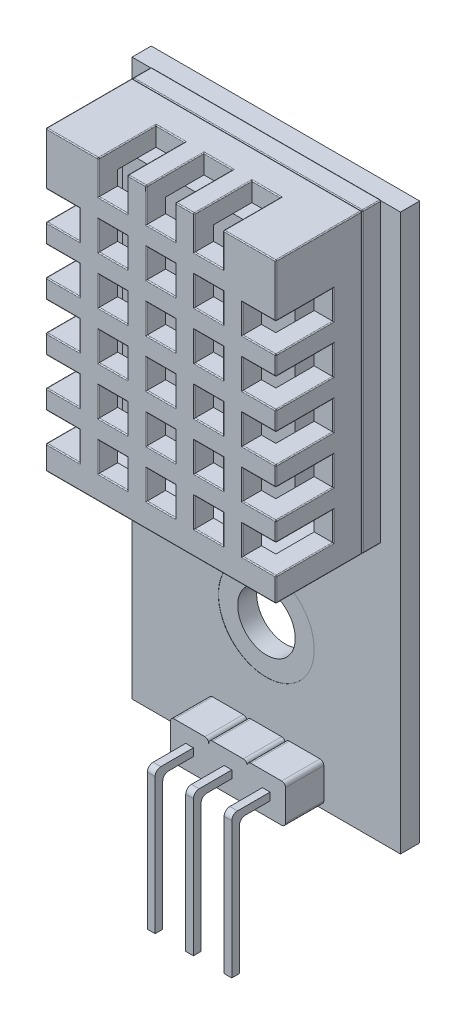
SolidWorks part; units mm, degrees
ref_plane "Front Plane" through (0, 0, 0) normal (0, 0, 1) x (1, 0, 0)
ref_plane "Top Plane" through (0, 0, 0) normal (0, 1, 0) x (1, 0, 0)
ref_plane "Right Plane" through (0, 0, 0) normal (1, 0, 0) x (0, 0, -1)
sketch "Sketch1" plane through (0, 0, 0) normal (0, 0, 1) x (1, 0, 0)
  line L1 (0, 0) -> (12, 0)
  line L2 (0, 0) -> (0, 15.5)
  line L3 (0, 15.5) -> (12, 15.5)
  line L4 (12, 0) -> (12, 15.5)
  dimension "D1" = 12
  dimension "D2" = 15.5
extrude "Boss-Extrude1" add sketch "Sketch1" along normal blind 5.5
shell "Shell2" thickness 1 removed face at (6, 7.75, 0)
sketch "Sketch3" plane through (0, 0, 5.5) normal (0, 0, 1) x (1, 0, 0)
  line L0 (12, 15.5) -> (0, 15.5) construction
  line L1 (2.75, 15.5) -> (4.25, 15.5)
  line L2 (2.75, 15.5) -> (2.75, 13.75)
  line L3 (2.75, 13.75) -> (4.25, 13.75)
  line L4 (4.25, 15.5) -> (4.25, 13.75)
  line L5 (5.25, 15.5) -> (6.75, 15.5)
  line L6 (5.25, 15.5) -> (5.25, 13.75)
  line L7 (5.25, 13.75) -> (6.75, 13.75)
  line L8 (6.75, 15.5) -> (6.75, 13.75)
  line L9 (7.75, 15.5) -> (9.25, 15.5)
  line L10 (7.75, 15.5) -> (7.75, 13.75)
  line L11 (7.75, 13.75) -> (9.25, 13.75)
  line L12 (9.25, 15.5) -> (9.25, 13.75)
  line L13 (0, 15.5) -> (0, 0) construction
  dimension "D1" = 1.5
  dimension "D2" = 1.75
  dimension "D4" = 2.75
  dimension "D3" = 3
extrude "Cut-Extrude1" cut sketch "Sketch3" against normal blind 3
sketch "Sketch4" plane through (0, 0, 5.5) normal (0, 0, 1) x (1, 0, 0)
  line L0 (2.75, 13.75) -> (4.25, 13.75) construction
  line L1 (2.75, 12.75) -> (4.25, 12.75)
  line L2 (2.75, 12.75) -> (2.75, 11.25)
  line L3 (2.75, 11.25) -> (4.25, 11.25)
  line L4 (4.25, 12.75) -> (4.25, 11.25)
  line L5 (0, 15.5) -> (0, 0) construction
  line L6 (5.25, 12.75) -> (6.75, 12.75)
  line L7 (5.25, 12.75) -> (5.25, 11.25)
  line L8 (5.25, 11.25) -> (6.75, 11.25)
  line L9 (6.75, 12.75) -> (6.75, 11.25)
  line L10 (7.75, 12.75) -> (9.25, 12.75)
  line L11 (7.75, 12.75) -> (7.75, 11.25)
  line L12 (7.75, 11.25) -> (9.25, 11.25)
  line L13 (9.25, 12.75) -> (9.25, 11.25)
  line L14 (5.25, 10.25) -> (6.75, 10.25)
  line L15 (5.25, 10.25) -> (5.25, 8.75)
  line L16 (5.25, 8.75) -> (6.75, 8.75)
  line L17 (6.75, 10.25) -> (6.75, 8.75)
  line L18 (7.75, 10.25) -> (9.25, 10.25)
  line L19 (7.75, 10.25) -> (7.75, 8.75)
  line L20 (7.75, 8.75) -> (9.25, 8.75)
  line L21 (9.25, 10.25) -> (9.25, 8.75)
  line L22 (5.25, 7.75) -> (6.75, 7.75)
  line L23 (5.25, 7.75) -> (5.25, 6.25)
  line L24 (5.25, 6.25) -> (6.75, 6.25)
  line L25 (6.75, 7.75) -> (6.75, 6.25)
  line L26 (7.75, 7.75) -> (9.25, 7.75)
  line L27 (7.75, 7.75) -> (7.75, 6.25)
  line L28 (7.75, 6.25) -> (9.25, 6.25)
  line L29 (9.25, 7.75) -> (9.25, 6.25)
  line L30 (5.25, 5.25) -> (6.75, 5.25)
  line L31 (5.25, 5.25) -> (5.25, 3.75)
  line L32 (5.25, 3.75) -> (6.75, 3.75)
  line L33 (6.75, 5.25) -> (6.75, 3.75)
  line L34 (7.75, 5.25) -> (9.25, 5.25)
  line L35 (7.75, 5.25) -> (7.75, 3.75)
  line L36 (7.75, 3.75) -> (9.25, 3.75)
  line L37 (9.25, 5.25) -> (9.25, 3.75)
  line L38 (5.25, 2.75) -> (6.75, 2.75)
  line L39 (5.25, 2.75) -> (5.25, 1.25)
  line L40 (5.25, 1.25) -> (6.75, 1.25)
  line L41 (6.75, 2.75) -> (6.75, 1.25)
  line L42 (7.75, 2.75) -> (9.25, 2.75)
  line L43 (7.75, 2.75) -> (7.75, 1.25)
  line L44 (7.75, 1.25) -> (9.25, 1.25)
  line L45 (9.25, 2.75) -> (9.25, 1.25)
  line L46 (2.75, 10.25) -> (4.25, 10.25)
  line L47 (2.75, 10.25) -> (2.75, 8.75)
  line L48 (2.75, 8.75) -> (4.25, 8.75)
  line L49 (4.25, 10.25) -> (4.25, 8.75)
  line L50 (2.75, 7.75) -> (4.25, 7.75)
  line L51 (2.75, 7.75) -> (2.75, 6.25)
  line L52 (2.75, 6.25) -> (4.25, 6.25)
  line L53 (4.25, 7.75) -> (4.25, 6.25)
  line L54 (2.75, 5.25) -> (4.25, 5.25)
  line L55 (2.75, 5.25) -> (2.75, 3.75)
  line L56 (2.75, 3.75) -> (4.25, 3.75)
  line L57 (4.25, 5.25) -> (4.25, 3.75)
  line L58 (2.75, 2.75) -> (4.25, 2.75)
  line L59 (2.75, 2.75) -> (2.75, 1.25)
  line L60 (2.75, 1.25) -> (4.25, 1.25)
  line L61 (4.25, 2.75) -> (4.25, 1.25)
  dimension "D1" = 1.5
  dimension "D2" = 1
  dimension "D3" = 2.75
  dimension "D4" = 3
  dimension "D5" = 5
extrude "Cut-Extrude2" cut sketch "Sketch4" against normal blind 3
sketch "Sketch5" plane through (0, 0, 5.5) normal (0, 0, 1) x (1, 0, 0)
  line L0 (0, 15.5) -> (0, 0) construction
  line L1 (0, 12.75) -> (1.75, 12.75)
  line L2 (0, 12.75) -> (0, 11.25)
  line L3 (0, 11.25) -> (1.75, 11.25)
  line L4 (1.75, 12.75) -> (1.75, 11.25)
  line L7 (2.75, 12.75) -> (2.75, 11.25) construction
  line L8 (10.25, 12.75) -> (12, 12.75)
  line L9 (10.25, 12.75) -> (10.25, 11.25)
  line L10 (10.25, 11.25) -> (12, 11.25)
  line L11 (12, 12.75) -> (12, 11.25)
  line L12 (10.25, 10.25) -> (12, 10.25)
  line L13 (10.25, 10.25) -> (10.25, 8.75)
  line L14 (10.25, 8.75) -> (12, 8.75)
  line L15 (12, 10.25) -> (12, 8.75)
  line L16 (10.25, 7.75) -> (12, 7.75)
  line L17 (10.25, 7.75) -> (10.25, 6.25)
  line L18 (10.25, 6.25) -> (12, 6.25)
  line L19 (12, 7.75) -> (12, 6.25)
  line L20 (10.25, 5.25) -> (12, 5.25)
  line L21 (10.25, 5.25) -> (10.25, 3.75)
  line L22 (10.25, 3.75) -> (12, 3.75)
  line L23 (12, 5.25) -> (12, 3.75)
  line L24 (10.25, 2.75) -> (12, 2.75)
  line L25 (10.25, 2.75) -> (10.25, 1.25)
  line L26 (10.25, 1.25) -> (12, 1.25)
  line L27 (12, 2.75) -> (12, 1.25)
  line L28 (0, 10.25) -> (1.75, 10.25)
  line L29 (0, 10.25) -> (0, 8.75)
  line L30 (0, 8.75) -> (1.75, 8.75)
  line L31 (1.75, 10.25) -> (1.75, 8.75)
  line L32 (0, 7.75) -> (1.75, 7.75)
  line L33 (0, 7.75) -> (0, 6.25)
  line L34 (0, 6.25) -> (1.75, 6.25)
  line L35 (1.75, 7.75) -> (1.75, 6.25)
  line L36 (0, 5.25) -> (1.75, 5.25)
  line L37 (0, 5.25) -> (0, 3.75)
  line L38 (0, 3.75) -> (1.75, 3.75)
  line L39 (1.75, 5.25) -> (1.75, 3.75)
  line L40 (0, 2.75) -> (1.75, 2.75)
  line L41 (0, 2.75) -> (0, 1.25)
  line L42 (0, 1.25) -> (1.75, 1.25)
  line L43 (1.75, 2.75) -> (1.75, 1.25)
  dimension "D1" = 1
  dimension "D2" = 2
  dimension "D3" = 5
extrude "Cut-Extrude3" cut sketch "Sketch5" against normal blind 3
sketch "Sketch6" plane through (0, 0, 0) normal (0, 0, -1) x (-1, 0, 0)
  line L4 (0, 0) -> (0, 15.5)
  line L5 (0, 15.5) -> (-12, 15.5)
  line L6 (-12, 15.5) -> (-12, 0)
  line L7 (-12, 0) -> (0, 0)
  line L8 (0, 0) -> (0, 15.5)
  line L9 (0, 15.5) -> (-12, 15.5)
  line L10 (-12, 15.5) -> (-12, 0)
  line L11 (-12, 0) -> (0, 0)
  line L12 (-1, 14.5) -> (-11, 14.5)
  line L13 (-1, 1) -> (-1, 14.5)
  line L14 (-11, 1) -> (-1, 1)
  line L15 (-11, 14.5) -> (-11, 1)
  line L16 (-1, 14.5) -> (-11, 14.5)
  line L17 (-1, 1) -> (-1, 14.5)
  line L18 (-11, 1) -> (-1, 1)
  line L19 (-11, 14.5) -> (-11, 1)
  dimension "D1" = 0
  dimension "D2" = 0
extrude "Cut-Extrude4" cut sketch "Sketch6" against normal blind 1
ref_plane "Plane1" through (0, 0, 0.99) normal (0, 0, 1) x (1, 0, 0)
sketch "Sketch8" plane through (0, 0, 0.99) normal (0, 0, 1) x (1, 0, 0)
  line L4 (0, 0) -> (12, 0)
  line L5 (0, 15.5) -> (0, 0)
  line L6 (12, 15.5) -> (0, 15.5)
  line L7 (12, 0) -> (12, 15.5)
  line L8 (0, 0) -> (12, 0)
  line L9 (0, 15.5) -> (0, 0)
  line L10 (12, 15.5) -> (0, 15.5)
  line L11 (12, 0) -> (12, 15.5)
  dimension "D1" = 0
extrude "Boss-Extrude3" add sketch "Sketch8" against normal blind 0.99 separate body
fillet "Fillet1" radius 0.05 163 edges at (6, 0, 1) (0, 12.75, 4) (0, 12, 2.5) (0, 11.25, 4) (0, 10.25, 4) (0, 9.5, 2.5) (0, 8.75, 4) (0, 7.75, 4) (0, 7, 2.5) (0, 6.25, 4) (0, 5.25, 4) (0, 4.5, 2.5) (0, 3.75, 4) (0, 2.75, 4) (0, 2, 2.5) (0, 1.25, 4) (0, 0, 3.25) (0, 7.75, 1) (9.25, 15.5, 4) (8.5, 15.5, 2.5) (7.75, 15.5, 4) (6.75, 15.5, 4) (6, 15.5, 2.5) (5.25, 15.5, 4) (4.25, 15.5, 4) (3.5, 15.5, 2.5) (2.75, 15.5, 4) (0, 15.5, 3.25) (6, 15.5, 1) (12, 0, 3.25) (12, 1.25, 4) (12, 2, 2.5) (12, 2.75, 4) (12, 3.75, 4) (12, 4.5, 2.5) (12, 5.25, 4) (12, 6.25, 4) (12, 7, 2.5) (12, 7.75, 4) (12, 8.75, 4) (12, 9.5, 2.5) (12, 10.25, 4) (12, 11.25, 4) (12, 12, 2.5) (12, 12.75, 4) (12, 15.5, 3.25) (12, 7.75, 1) (0.875, 3.75, 5.5) (1.75, 4.5, 5.5) (0.875, 5.25, 5.5) (0, 5.75, 5.5) (0.875, 6.25, 5.5) (1.75, 7, 5.5) (0.875, 7.75, 5.5) (0, 8.25, 5.5) (0.875, 8.75, 5.5) (1.75, 9.5, 5.5) (0.875, 10.25, 5.5) (0, 10.75, 5.5) (0.875, 11.25, 5.5) (1.75, 12, 5.5) (0.875, 12.75, 5.5) (0, 14.125, 5.5) (1.375, 15.5, 5.5) (2.75, 14.625, 5.5) (3.5, 13.75, 5.5) (4.25, 14.625, 5.5) (4.75, 15.5, 5.5) (5.25, 14.625, 5.5) (6, 13.75, 5.5) (6.75, 14.625, 5.5) (7.25, 15.5, 5.5) (7.75, 14.625, 5.5) (8.5, 13.75, 5.5) (9.25, 14.625, 5.5) (10.625, 15.5, 5.5) (12, 14.125, 5.5) (11.125, 12.75, 5.5) (10.25, 12, 5.5) (11.125, 11.25, 5.5) (12, 10.75, 5.5) (11.125, 10.25, 5.5) (10.25, 9.5, 5.5) (11.125, 8.75, 5.5) (12, 8.25, 5.5) (11.125, 7.75, 5.5) (10.25, 7, 5.5) (11.125, 6.25, 5.5) (12, 5.75, 5.5) (11.125, 5.25, 5.5) (10.25, 4.5, 5.5) (11.125, 3.75, 5.5) (12, 3.25, 5.5) (11.125, 2.75, 5.5) (10.25, 2, 5.5) (11.125, 1.25, 5.5) (12, 0.625, 5.5) (6, 0, 5.5) (0, 0.625, 5.5) (0.875, 1.25, 5.5) (1.75, 2, 5.5) (0.875, 2.75, 5.5) (0, 3.25, 5.5) (4.25, 12, 5.5) (3.5, 12.75, 5.5) (2.75, 12, 5.5) (3.5, 11.25, 5.5) (6.75, 12, 5.5) (6, 12.75, 5.5) (5.25, 12, 5.5) (6, 11.25, 5.5) (9.25, 12, 5.5) (8.5, 12.75, 5.5) (7.75, 12, 5.5) (8.5, 11.25, 5.5) (6.75, 9.5, 5.5) (6, 10.25, 5.5) (5.25, 9.5, 5.5) (6, 8.75, 5.5) (9.25, 9.5, 5.5) (8.5, 10.25, 5.5) (7.75, 9.5, 5.5) (8.5, 8.75, 5.5) (6.75, 7, 5.5) (6, 7.75, 5.5) (5.25, 7, 5.5) (6, 6.25, 5.5) (9.25, 7, 5.5) (8.5, 7.75, 5.5) (7.75, 7, 5.5) (8.5, 6.25, 5.5) (6.75, 4.5, 5.5) (6, 5.25, 5.5) (5.25, 4.5, 5.5) (6, 3.75, 5.5) (9.25, 4.5, 5.5) (8.5, 5.25, 5.5) (7.75, 4.5, 5.5) (8.5, 3.75, 5.5) (6.75, 2, 5.5) (6, 2.75, 5.5) (5.25, 2, 5.5) (6, 1.25, 5.5) (9.25, 2, 5.5) (8.5, 2.75, 5.5) (7.75, 2, 5.5) (8.5, 1.25, 5.5) (4.25, 9.5, 5.5) (3.5, 10.25, 5.5) (2.75, 9.5, 5.5) (3.5, 8.75, 5.5) (4.25, 7, 5.5) (3.5, 7.75, 5.5) (2.75, 7, 5.5) (3.5, 6.25, 5.5) (4.25, 4.5, 5.5) (3.5, 5.25, 5.5) (2.75, 4.5, 5.5) (3.5, 3.75, 5.5) (4.25, 2, 5.5) (3.5, 2.75, 5.5) (2.75, 2, 5.5) (3.5, 1.25, 5.5)
fillet "Fillet2" radius 0.05 12 edges at (6, 15.5, 0.99) (0, 15.5, 0.495) (0, 7.75, 0.99) (0, 0, 0.495) (6, 0, 0.99) (12, 15.5, 0.495) (12, 0, 0.495) (12, 7.75, 0.99) (6, 15.5, 0) (0, 7.75, 0) (6, 0, 0) (12, 7.75, 0)
sketch "Sketch10" plane through (0, 0, 0.99) normal (0, 0, 1) x (1, 0, 0)
  line L14 (1.5, 1.5) -> (10.5, 1.5)
  line L15 (10.5, 1.5) -> (10.5, 14)
  line L16 (10.5, 14) -> (1.5, 14)
  line L17 (1.5, 14) -> (1.5, 1.5)
  line L18 (1.5, 1.5) -> (10.5, 1.5)
  line L19 (10.5, 1.5) -> (10.5, 14)
  line L20 (10.5, 14) -> (1.5, 14)
  line L21 (1.5, 14) -> (1.5, 1.5)
  dimension "D1" = 0.5
extrude "Boss-Extrude4" add sketch "Sketch10" along normal blind 2
sketch "Sketch11" plane through (0, 0, 0) normal (0, 0, -1) x (-1, 0, 0)
  line L0 (-11.95, 0.05) -> (-0.05, 0.05) construction
  line L1 (-13, 15.45) -> (1, 15.45)
  line L2 (-13, 15.45) -> (-13, -13.55)
  line L3 (-13, -13.55) -> (1, -13.55)
  line L4 (1, 15.45) -> (1, -13.55)
  point P4 (-6, 15.45)
  point P7 (-6, 0.05)
  dimension "D1" = 14
  dimension "D2" = 29
  dimension "D3" = 0
  dimension "D4" = 14
extrude "Boss-Extrude5" add sketch "Sketch11" along normal blind 1
sketch "Sketch12" plane through (0, 0, 0) normal (0, 0, 1) x (1, 0, 0)
  line L2 (3, -11.55) -> (3, -13.15)
  line L4 (9, -11.55) -> (9, -13.15)
  line L5 (13, 15.45) -> (13, -13.55) construction
  line L7 (5, -11.55) -> (5, -13.15)
  line L8 (7, -11.55) -> (7, -13.15)
  line L9 (3.2, -11.35) -> (4.8, -11.35)
  line L10 (6.8, -11.35) -> (5.2, -11.35)
  line L11 (8.8, -11.35) -> (7.2, -11.35)
  line L12 (9, -13.35) -> (9, -11.35)
  line L13 (8.8, -13.35) -> (7.2, -13.35)
  line L14 (6.8, -13.35) -> (5.2, -13.35)
  line L15 (4.8, -13.35) -> (3.2, -13.35)
  arc A0 (3, -11.55) -> (3.2, -11.35) centre (3.2, -11.55) cw
  arc A1 (5, -11.55) -> (4.8, -11.35) centre (4.8, -11.55) ccw
  arc A2 (5, -11.55) -> (5.2, -11.35) centre (5.2, -11.55) cw
  arc A3 (3.2, -13.35) -> (3, -13.15) centre (3.2, -13.15) cw
  arc A4 (4.8, -13.35) -> (5, -13.15) centre (4.8, -13.15) ccw
  arc A5 (5, -13.15) -> (5.2, -13.35) centre (5.2, -13.15) ccw
  arc A6 (7, -13.15) -> (6.8, -13.35) centre (6.8, -13.15) cw
  arc A7 (7, -13.15) -> (7.2, -13.35) centre (7.2, -13.15) ccw
  arc A8 (7, -11.55) -> (6.8, -11.35) centre (6.8, -11.55) ccw
  arc A9 (7, -11.55) -> (7.2, -11.35) centre (7.2, -11.55) cw
  arc A10 (9, -11.55) -> (8.8, -11.35) centre (8.8, -11.55) ccw
  arc A11 (9, -13.15) -> (8.8, -13.35) centre (8.8, -13.15) cw
  point P8 (3, -11.35)
  dimension "D3" = 0.2
  dimension "D5" = 0.2
  dimension "D6" = 0.2
  dimension "D8" = 0.2
  dimension "D9" = 0.2
  dimension "D10" = 0.2
  dimension "D11" = 0.2
  dimension "D12" = 0.2
  dimension "D13" = 0.2
  dimension "D14" = 0.2
  dimension "D15" = 0.2
  dimension "D16" = 0.2
  dimension "D1" = 6
  dimension "D2" = 2
  dimension "D4" = 4
  dimension "D7" = 2
extrude "Boss-Extrude6" add sketch "Sketch12" along normal blind 2 contours L15 A4 L7 A1 L9 A0 L2 A3 | L8 A8 L10 A2 L7 A5 L14 A6 | A11 L4 A10 L11 A9 L8 A7 L13 region at (4, -12.35, 0) region at (6, -12.35, 0) region at (8, -12.35, 0)
sketch "Sketch13" plane through (0, 0, 2) normal (0, 0, 1) x (1, 0, 0)
  line L0 (3.2, -11.35) -> (4.8, -11.35) construction
  line L1 (3.8, -12.1506) -> (4.2, -12.1506)
  line L2 (3.8, -12.1506) -> (3.8, -12.5494)
  line L3 (3.8, -12.5494) -> (4.2, -12.5494)
  line L4 (4.2, -12.1506) -> (4.2, -12.5494)
  line L5 (3, -11.55) -> (3, -13.15) construction
  line L6 (6.8, -11.35) -> (5.2, -11.35) construction
  line L7 (5.8, -12.1506) -> (6.2, -12.1506)
  line L8 (5.8, -12.1506) -> (5.8, -12.5494)
  line L9 (5.8, -12.5494) -> (6.2, -12.5494)
  line L10 (6.2, -12.1506) -> (6.2, -12.5494)
  line L11 (8.8, -11.35) -> (7.2, -11.35) construction
  line L12 (7.8, -12.1506) -> (8.2, -12.1506)
  line L13 (7.8, -12.1506) -> (7.8, -12.5494)
  line L14 (7.8, -12.5494) -> (8.2, -12.5494)
  line L15 (8.2, -12.1506) -> (8.2, -12.5494)
  point P4 (4, -12.1506)
  point P7 (4, -11.35)
  point P8 (3.8, -12.35)
  point P11 (3, -12.35)
  point P16 (6, -12.1506)
  point P19 (6, -11.35)
  point P24 (8, -12.1506)
  point P27 (8, -11.35)
  dimension "D1" = 0.4
  dimension "D2" = 0.3988
  dimension "D3" = 0
  dimension "D4" = 0
  dimension "D5" = 0.4
  dimension "D6" = 0
  dimension "D7" = 0.4
  dimension "D8" = 0
extrude "Boss-Extrude7" add sketch "Sketch13" along normal blind 2
sketch "Sketch14" plane through (0, -12.5494, 0) normal (0, -1, 0) x (1, 0, 0)
  line L0 (6.2, 4) -> (6.2, 2) construction
  line L1 (5.8, 4) -> (6.2, 4)
  line L2 (5.8, 4) -> (5.8, 3.5997)
  line L3 (5.8, 3.5997) -> (6.2, 3.5997)
  line L4 (6.2, 4) -> (6.2, 3.5997)
  line L5 (4.2, 4) -> (4.2, 2) construction
  line L6 (3.8, 4) -> (4.2, 4)
  line L7 (3.8, 4) -> (3.8, 3.5997)
  line L8 (3.8, 3.5997) -> (4.2, 3.5997)
  line L9 (4.2, 4) -> (4.2, 3.5997)
  line L10 (8.2, 4) -> (8.2, 2) construction
  line L11 (7.8, 4) -> (8.2, 4)
  line L12 (7.8, 4) -> (7.8, 3.5997)
  line L13 (7.8, 3.5997) -> (8.2, 3.5997)
  line L14 (8.2, 4) -> (8.2, 3.5997)
extrude "Boss-Extrude8" add sketch "Sketch14" along normal blind 7
fillet "Fillet3" radius 0.3 1 edges at (4, -12.5494, 3.5997) type face fillet first side face at (4, -12.5494, 2.7999) second side face at (4, -16.0494, 3.5997)
fillet "Fillet4" radius 0.3 1 edges at (6, -12.5494, 3.5997) type face fillet first side face at (6, -12.5494, 2.7999) second side face at (6, -16.0494, 3.5997)
fillet "Fillet5" radius 0.3 1 edges at (8, -12.5494, 3.5997) type face fillet first side face at (8, -12.5494, 2.7999) second side face at (8, -16.0494, 3.5997)
fillet "Fillet6" radius 0.3 1 edges at (4, -12.1506, 4) type face fillet first side face at (4, -12.1506, 3) second side face at (4, -15.85, 4)
fillet "Fillet7" radius 0.3 1 edges at (6, -12.1506, 4) type face fillet first side face at (6, -12.1506, 3) second side face at (6, -15.85, 4)
fillet "Fillet8" radius 0.3 1 edges at (8, -12.1506, 4) type face fillet first side face at (8, -12.1506, 3) second side face at (8, -15.85, 4)
sketch "Sketch15" plane through (0, 0, 0) normal (0, 0, 1) x (1, 0, 0)
  circle A0 centre (6, -6.5668) radius 1.5
  dimension "D1" = 3
extrude "Cut-Extrude5" cut sketch "Sketch15" against normal through all
sketch "Sketch16" plane through (0, 0, 0) normal (0, 0, 1) x (1, 0, 0)
  circle A0 centre (6, -6.5668) radius 2.5
  dimension "D1" = 5
extrude "Cut-Extrude6" cut sketch "Sketch16" against normal blind 0.01
